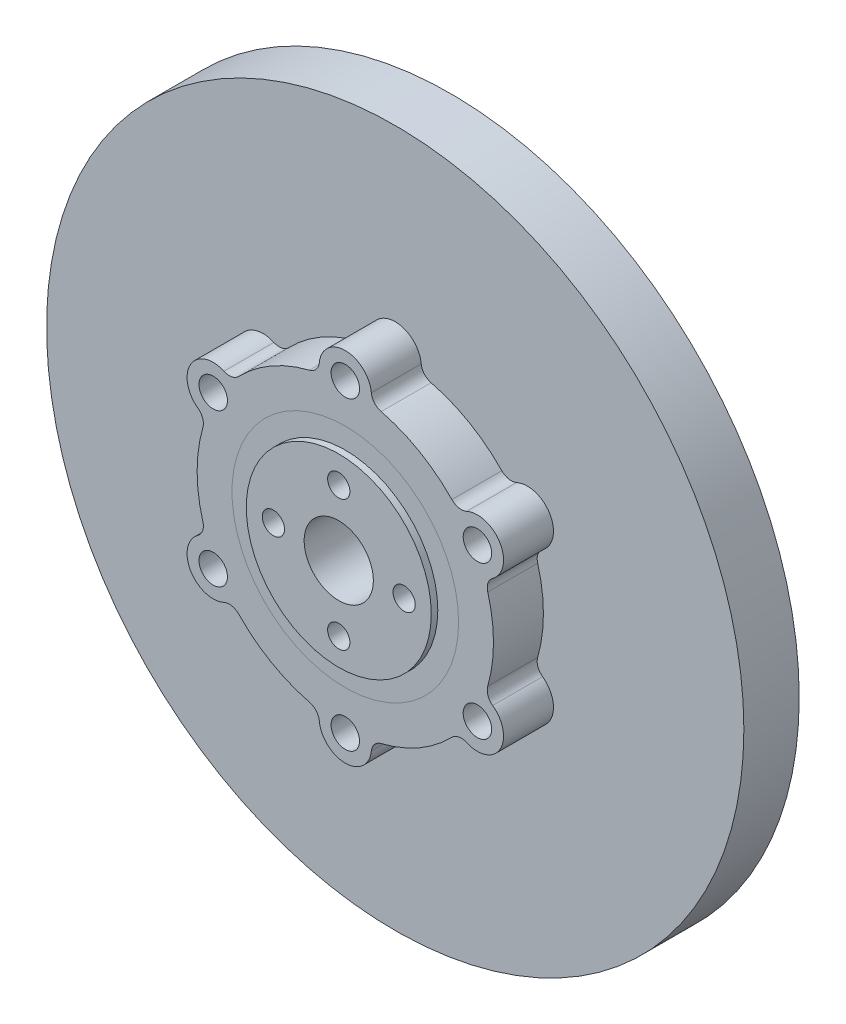
SolidWorks part; units mm, degrees
ref_plane "Front Plane" through (0, 0, 0) normal (0, 0, 1) x (1, 0, 0)
ref_plane "Top Plane" through (0, 0, 0) normal (0, 1, 0) x (1, 0, 0)
ref_plane "Right Plane" through (0, 0, 0) normal (1, 0, 0) x (0, 0, -1)
sketch "Sketch2" plane through (0, 0, 0) normal (0, 1, 0) x (1, 0, 0)
  line L0 (0, 0) -> (0, 53.8667) construction
  line L1 (0, 0) -> (-90.2095, 0) construction
  line L2 (-80, 6.35) -> (-80, -6.35)
  line L3 (-80, -6.35) -> (-30, -6.35)
  line L5 (-30, 6.35) -> (-80, 6.35)
  line L6 (-53.089, -19.304) -> (-7.9375, -19.304) construction
  line L7 (-20, -10.804) -> (-10, -10.804)
  line L8 (-20, -10.804) -> (-20, -17.804)
  line L9 (-21.2263, -19.304) -> (-7.9375, -19.304)
  line L10 (20, -10.804) -> (20, -19.304) construction
  line L11 (21, -8.804) -> (-21, -8.804) construction
  line L12 (21, -8.804) -> (21, 6.196) construction
  line L13 (21, 6.196) -> (-21, 6.196) construction
  line L14 (-21, -8.804) -> (-21, 6.196) construction
  line L15 (21, -8.804) -> (-21, 6.196) construction
  line L16 (21, 6.196) -> (-21, -8.804) construction
  line L17 (-92.5642, 19.304) -> (88.6804, 19.304) construction
  line L18 (-20, -10.804) -> (-26, -10.804)
  line L19 (-26, -10.804) -> (-26, -17.804)
  line L20 (-26, -17.804) -> (-20, -17.804)
  line L25 (-26, -17.804) -> (-34, -17.804)
  line L26 (-34, -17.804) -> (-34, -6.35)
  line L27 (-34, -6.35) -> (-30, -6.35)
  line L28 (-30, -6.35) -> (-30, 18.554)
  line L29 (-10, -10.804) -> (-10, 8.554)
  line L30 (-17.5, 18.554) -> (-8.5, 18.554)
  line L31 (-21.7937, 8.554) -> (-17.5, 8.554)
  line L32 (-30, 18.554) -> (-17.5, 18.554)
  line L33 (-21.7937, 8.554) -> (-21.7937, -10.804)
  line L34 (-17.5, 18.554) -> (-17.5, 8.554)
  line L35 (-7.9375, -10.804) -> (-7.9375, -19.304)
  line L36 (-17.5, 8.554) -> (-8.5, 8.554)
  line L37 (-8.5, 18.554) -> (-8.5, 8.554)
  line L38 (-10, 8.554) -> (-8.5, 8.554)
  line L39 (-8.5, 8.554) -> (-8.5, 19.304)
  line L40 (-8.5, 19.304) -> (-7.9375, 19.304)
  line L41 (-7.9375, 19.304) -> (-7.9375, -10.804)
  line L44 (-7.9375, -10.804) -> (20, -10.804) construction
  line L45 (-7.9375, -19.304) -> (20, -19.304) construction
  line L46 (20, -19.304) -> (82.4175, -19.304) construction
  line L47 (-7.9375, -19.304) -> (20, -19.304) construction
  line L48 (-21.2263, -19.304) -> (-21.2263, -17.804)
  line L49 (-21.2263, -17.804) -> (-20, -17.804)
  line L50 (-20, -17.804) -> (-20, -19.304) construction
  line L51 (-21.7937, 8.554) -> (-17.5, 8.554)
  point P13 (0, -1.304)
  dimension "D1" = 160
  dimension "D2" = 12.7
  dimension "D3" = 38.608
  dimension "D4" = 42
  dimension "D5" = 15
  dimension "D6" = 40
  dimension "D7" = 7
  dimension "D8" = 1.5
  dimension "D9" = 52
  dimension "D10" = 68
  dimension "D11" = 4
  dimension "D12" = 17
  dimension "D13" = 35
  dimension "D14" = 10
  dimension "D15" = 2
  dimension "D16" = 1.5
  dimension "D17" = 15.875
  dimension "D18" = 20
revolve "Revolve1" add sketch "Sketch2" angle 360 about L0 region at (-26.093, 0, -1.5704)
revolve "Revolve2" add sketch "Sketch2<5>" angle 360 about L0 region at (-55, 0, 0)
sketch "Sketch2<5>" plane through (0, 0, 0) normal (0, 1, 0) x (1, 0, 0) same geometry as "Sketch2"
revolve "Revolve3" add sketch "Sketch2<7>" angle 360 about L0 region at (-8.0917, 0, -18.929)
sketch "Sketch2<7>" plane through (0, 0, 0) normal (0, 1, 0) x (1, 0, 0) same geometry as "Sketch2"
revolve "Revolve4" add sketch "Sketch2<8>" angle 360 about L0 region at (-13, 0, -13.554) region at (-23, 0, 14.304)
sketch "Sketch2<8>" plane through (0, 0, 0) normal (0, 1, 0) x (1, 0, 0) same geometry as "Sketch2"
sketch "Sketch3" plane through (0, 0, 17.804) normal (0, 0, 1) x (1, 0, 0)
  circle A0 centre (0, 35) radius 6
  circle A1 centre (30.3109, 17.5) radius 6
  circle A2 centre (30.3109, -17.5) radius 6
  circle A3 centre (0, -35) radius 6
  circle A4 centre (-30.3109, -17.5) radius 6
  circle A5 centre (-30.3109, 17.5) radius 6
  circle A7 centre (0, 0) radius 35 construction
  point P15 (0, 0)
  dimension "D1" = 6
  dimension "D2" = 70
  dimension "D3" = 12
extrude "Boss-Extrude1" add sketch "Sketch3" against normal up to surface (24.154 mm away) up to face at (80, 0, -6.35)
fillet "Fillet1" radius 3 12 edges at (-5.8095, 33.5, 12.077) (5.8095, 33.5, 12.077) (26.1071, 21.7812, 12.077) (26.1071, -21.7812, 12.077) (-5.8095, -33.5, 12.077) (-26.1071, -21.7812, 12.077) (-31.9166, -11.7188, 12.077) (-26.1071, 21.7812, 12.077) (-31.9166, 11.7188, 12.077) (5.8095, -33.5, 12.077) (31.9166, -11.7188, 12.077) (31.9166, 11.7188, 12.077)
fillet "Fillet2" radius 8 12 edges at (3.0666, -29.8429, 0) (-24.3114, -17.5772, 0) (-24.3114, 17.5772, 0) (-3.0666, 29.8429, 0) (24.3114, 17.5772, 0) (27.378, 12.2657, 0) (3.0666, 29.8429, 0) (-27.378, 12.2657, 0) (-27.378, -12.2657, 0) (-3.0666, -29.8429, 0) (27.378, -12.2657, 0) (24.3114, -17.5772, 0)
sketch "Sketch6" plane through (0, 0, -6.35) normal (0, 0, -1) x (-1, 0, 0)
  arc A0 (5.9983, 35.1408) -> (-5.9983, 35.1408) centre (0, 35) ccw construction
  point P0 (-30.3109, 17.5)
  point P10 (0, 35)
  point P11 (30.3109, 17.5)
  point P12 (30.3109, -17.5)
  point P13 (0, -35)
  point P14 (-30.3109, -17.5)
  dimension "D1" = 6
hole_wizard "1/4-20 Tapped Hole1" positions "Sketch6" profile "Sketch7" tap size "1/4-20" standard "ANSI Inch" end condition through all
sketch "Sketch7" plane through (30.3109, 17.5, -6.35) normal (1, 0, 0) x (0, 1, 0)
  line L0 (0, 0) -> (0, 25.654)
  line L1 (0, 25.654) -> (2.5527, 25.654)
  line L2 (2.5527, 25.654) -> (2.5527, 0)
  line L5 (2.5527, 0) -> (0, 0)
  line L11 (0, -6.35) -> (0, 107.95) construction
  dimension "Thru Tap Drill Dia." = 5.1054
  dimension "Thru Tap Drill Depth" = 25.654
cosmetic thread "Hole Thread1"
cosmetic thread "Hole Thread2"
cosmetic thread "Hole Thread3"
cosmetic thread "Hole Thread4"
cosmetic thread "Hole Thread5"
cosmetic thread "Hole Thread6"
sketch "Sketch8" plane through (0, 0, -6.35) normal (0, 0, -1) x (-1, 0, 0)
  circle A1 centre (0, 0) radius 41
  circle A2 centre (0, 0) radius 30.25
  circle A3 centre (0, 0) radius 30.25
  arc A4 (5.9983, 35.1408) -> (-5.9983, 35.1408) centre (0, 35) ccw construction
  dimension "D1" = 0.25
extrude "Boss-Extrude2" add sketch "Sketch8" along normal blind 2
sketch "Sketch11" plane through (0, 0, -8.35) normal (0, 0, -1) x (-1, 0, 0)
  point P0 (0, 35)
  point P3 (30.3109, 17.5)
  point P6 (30.3109, -17.5)
  point P9 (0, -35)
  point P12 (-30.3109, -17.5)
  point P15 (-30.3109, 17.5)
hole_wizard "1/4 Clearance Hole1" positions "Sketch11" profile "Sketch13" hole size "1/4" standard "ANSI Inch" end condition through all
sketch "Sketch13" plane through (0, 35, -8.35) normal (1, 0, 0) x (0, 1, 0)
  line L0 (0, 0) -> (0, 27.654)
  line L1 (0, 27.654) -> (3.2639, 27.654)
  line L2 (3.2639, 27.654) -> (3.2639, 0)
  line L5 (3.2639, 0) -> (0, 0)
  line L11 (0, -6.35) -> (0, 107.95) construction
  dimension "Thru Hole Dia." = 6.5278
  dimension "Thru Hole Depth" = 27.654
sketch "Sketch9" plane through (0, 0, 19.304) normal (0, 0, 1) x (1, 0, 0)
  circle A0 centre (0, 0) radius 15 construction
  point P4 (0, 15)
  point P11 (15, 0)
  point P12 (0, -15)
  point P13 (-15, 0)
  dimension "D1" = 4
  dimension "D2" = 30
hole_wizard "1/4-20 Tapped Hole2" positions "Sketch9" profile "Sketch10" tap size "1/4-20" standard "ANSI Inch" end condition through all
sketch "Sketch10" plane through (-15, 0, 19.304) normal (1, 0, 0) x (0, -1, 0)
  line L0 (0, 0) -> (0, 38.608)
  line L1 (0, 38.608) -> (2.5527, 38.608)
  line L2 (2.5527, 38.608) -> (2.5527, 0)
  line L5 (2.5527, 0) -> (0, 0)
  line L11 (0, -6.35) -> (0, 107.95) construction
  dimension "Thru Tap Drill Dia." = 5.1054
  dimension "Thru Tap Drill Depth" = 38.608
cosmetic thread "Hole Thread7"
cosmetic thread "Hole Thread8"
cosmetic thread "Hole Thread9"
cosmetic thread "Hole Thread10"
chamfer "Chamfer1" distance 8 angle 45 1 edges at (30, 0, -18.554)
sketch "Sketch14" plane through (0, 0, 0) normal (0, 1, 0) x (1, 0, 0)
  line L0 (-10, -10.804) -> (-10, 8.554) construction
  line L1 (-10, -8.946) -> (-11.5, -8.946)
  line L2 (-10, -8.946) -> (-10, 6.054)
  line L3 (-10, 6.054) -> (-11.5, 6.054)
  line L4 (-21, -8.946) -> (-21, 6.054)
  line L5 (-19.5, 6.054) -> (-19.5, 7.554)
  line L6 (-19.5, 7.554) -> (-11.5, 7.554)
  line L7 (-11.5, 7.554) -> (-11.5, 6.054)
  line L8 (-11.5, -8.946) -> (-11.5, -10.446)
  line L9 (-11.5, -10.446) -> (-19.5, -10.446)
  line L10 (-19.5, -10.446) -> (-19.5, -8.946)
  line L11 (0, 0) -> (0, 26.9333) construction
  line L12 (0, 0) -> (0, 53.8667) construction
  line L13 (-21.7937, 8.554) -> (-17.5, 8.554) construction
  line L14 (-19.5, 6.054) -> (-21, 6.054)
  line L15 (-19.5, -8.946) -> (-21, -8.946)
  point P19 (-11.5, -10.804)
  dimension "D1" = 1.5
  dimension "D2" = 15
  dimension "D3" = 42
  dimension "D4" = 1.5
  dimension "D5" = 1.5
  dimension "D6" = 1
revolve "Revolve5" add sketch "Sketch14" angle 360 about L11
sketch "Sketch15" plane through (0, 0, 0) normal (0, 1, 0) x (1, 0, 0)
  line L0 (0, 0) -> (0, 36.3125) construction
  line L1 (-21.7937, -10.804) -> (-24.5, -10.804)
  line L2 (-21.7937, -10.804) -> (-21.7937, 8.554)
  line L3 (-21.7937, 8.554) -> (-24.5, 8.554)
  line L4 (-24.5, -10.804) -> (-24.5, 8.554)
  line L5 (0, 0) -> (0, 53.8667) construction
  line L6 (-21.7937, 8.554) -> (-17.5, 8.554) construction
  line L7 (-21.7937, 8.554) -> (-21.7937, -10.804) construction
  point P10 (-21.7937, 8.554)
  dimension "D1" = 49
revolve "Cut-Revolve1" cut sketch "Sketch15" angle 360 about L0
revolve "Revolve6" add sketch "Sketch15<2>" angle 360 about L0
sketch "Sketch15<2>" plane through (0, 0, 0) normal (0, 1, 0) x (1, 0, 0) same geometry as "Sketch15"
